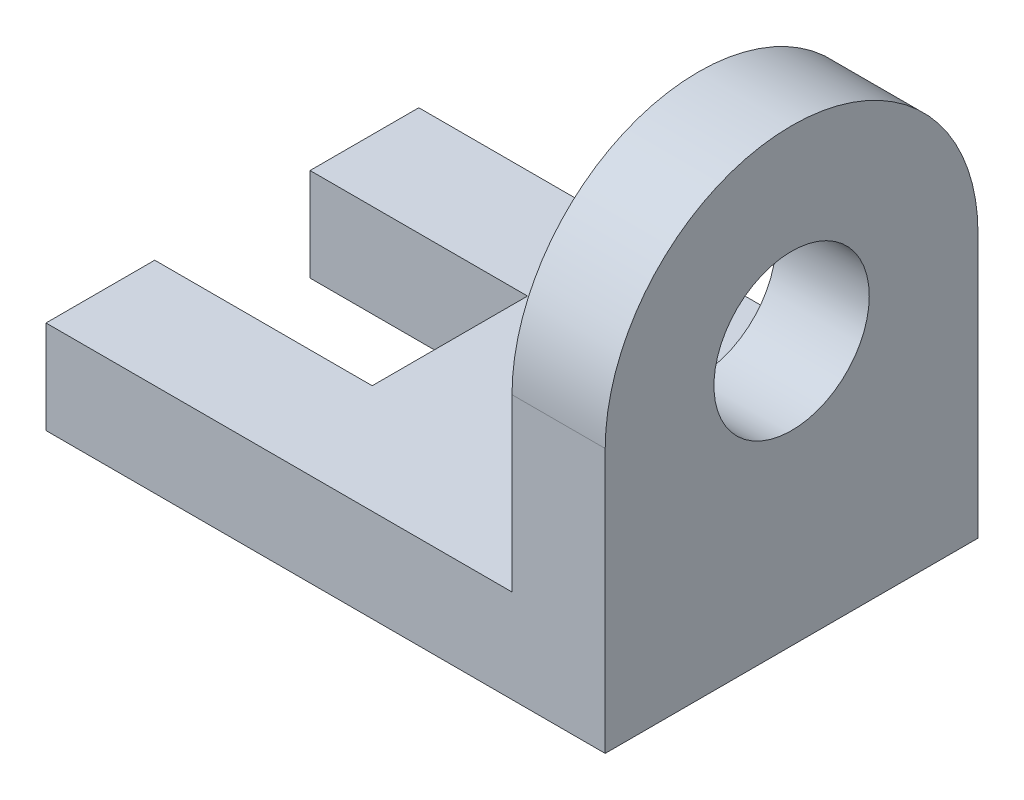
SolidWorks part; units mm, degrees
ref_plane "前视基准面" through (0, 0, 0) normal (0, 0, 1) x (1, 0, 0)
ref_plane "上视基准面" through (0, 0, 0) normal (0, 1, 0) x (1, 0, 0)
ref_plane "右视基准面" through (0, 0, 0) normal (1, 0, 0) x (0, 0, -1)
other "Configuration Table"
sketch "草图1" plane through (0, 0, 0) normal (0, 0, 1) x (1, 0, 0)
  line L0 (0, 0) -> (36, 0)
  line L1 (36, 0) -> (36, 29)
  line L2 (36, 29) -> (30, 29)
  line L3 (30, 29) -> (30, 6)
  line L4 (30, 6) -> (0, 6)
  line L5 (0, 6) -> (0, 0)
extrude "凸台-拉伸1" add sketch "草图1" along normal blind 24
sketch "草图2" plane through (0, 6, 0) normal (0, 1, 0) x (1, 0, 0)
  line L1 (0, -24) -> (0, 0) construction
  line L2 (0, -7) -> (14, -7)
  line L3 (14, -7) -> (14, -17)
  line L4 (14, -17) -> (0, -17)
  line L5 (0, -17) -> (0, -7)
extrude "切除-拉伸1" cut sketch "草图2" against normal blind 24
sketch "草图3" plane through (36, 0, 0) normal (1, 0, 0) x (0, 0, -1)
  line L0 (0, 29) -> (-24, 29)
  line L1 (-24, 29) -> (-24, 17)
  line L2 (-24, 0) -> (-24, 29) construction
  line L3 (0, 29) -> (0, 17)
  line L4 (0, 0) -> (0, 29) construction
  arc A0 (-24, 17) -> (0, 17) centre (-12, 17) cw
  line M1 (0, 0) -> (0, 29)
  line M2 (0, 29) -> (-24, 29)
  line M3 (-24, 29) -> (-24, 0)
extrude "切除-拉伸2" cut sketch "草图3" against normal blind 24 contours A0 L0 M3 | A0 M2 M1 region at (36, 26.3196, 2.6804) region at (36, 26.3196, 21.3196)
sketch "草图5" plane through (36, 0, 0) normal (1, 0, 0) x (0, 0, -1)
  circle A0 centre (-12, 17) radius 5
extrude "切除-拉伸3" cut sketch "草图5" against normal blind 24
